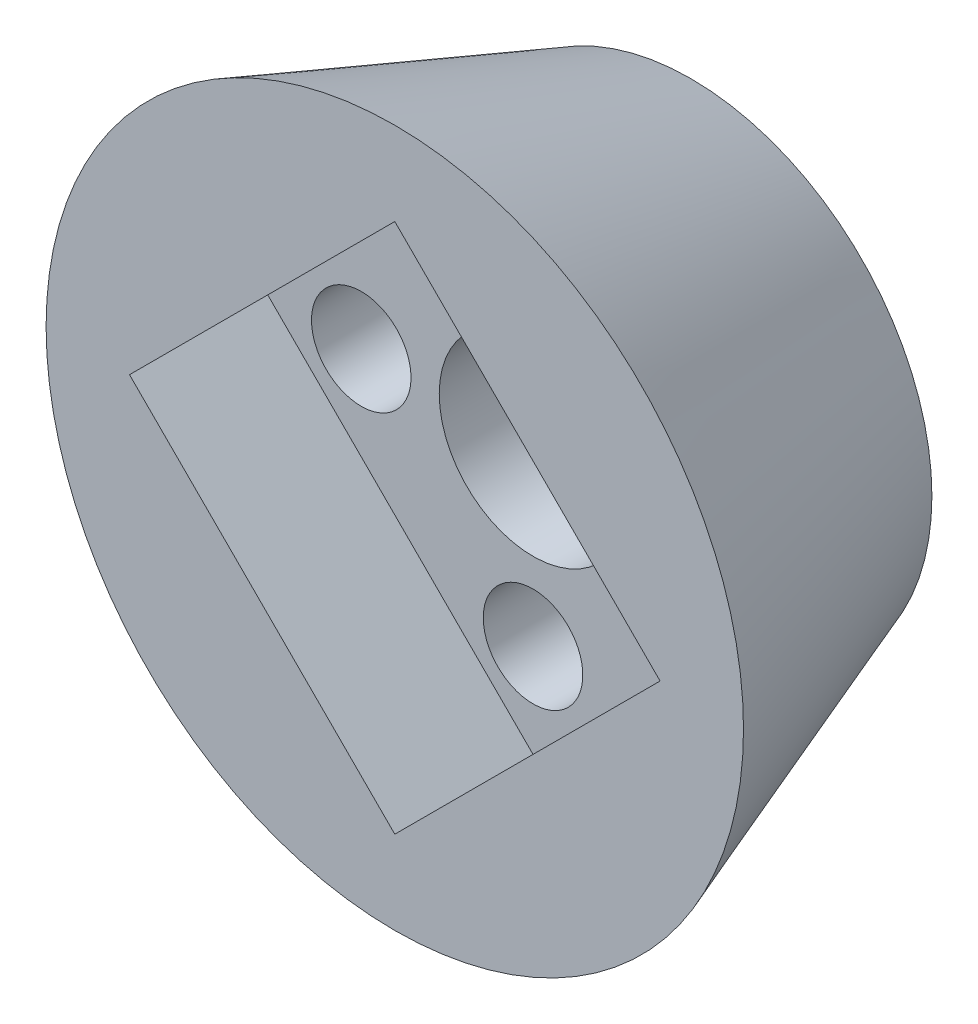
SolidWorks part; units mm, degrees
ref_plane "Front" through (0, 0, 0) normal (0, 0, 1) x (1, 0, 0)
ref_plane "Top" through (0, 0, 0) normal (0, 1, 0) x (1, 0, 0)
ref_plane "Right" through (0, 0, 0) normal (1, 0, 0) x (0, 0, -1)
sketch "GearFaceProfile" plane through (0, 0, 0) normal (0, 0, 1) x (1, 0, 0)
  circle A0 centre (0, 0) radius 12.2
  dimension "D1" = 24.4
extrude "GearFaceExtrude" add sketch "GearFaceProfile" along normal blind 15 draft 20 draft outward yes
sketch "CenterHoleProfile" plane through (0, 0, 0) normal (0, 0, -1) x (-1, 0, 0)
  circle A0 centre (0, 0) radius 4.75
  dimension "D1" = 9.5
extrude "CenterHoleCut" cut sketch "CenterHoleProfile" against normal through all
sketch "ScrewHoleProfile" plane through (0, 0, 0) normal (0, 0, -1) x (-1, 0, 0)
  line L0 (0, 0) -> (0, 8.7) construction
  line L1 (0, 0) -> (8.7, 0) construction
  line L2 (0, 0) -> (0, -8.7) construction
  line L3 (0, 0) -> (-8.7, 0) construction
  circle A2 centre (0, 8.7) radius 2.52
  circle A3 centre (8.7, 0) radius 2.52
  circle A4 centre (0, -8.7) radius 2.52
  circle A5 centre (-8.7, 0) radius 2.52
  dimension "D5" = 5.04
  dimension "D6" = 5.04
  dimension "D7" = 5.04
  dimension "D8" = 5.04
  dimension "D1" = 8.7
  dimension "D2" = 8.7
  dimension "D3" = 8.7
  dimension "D4" = 8.7
extrude "ScrewHoleCut" cut sketch "ScrewHoleProfile" against normal through all
sketch "ShaftCollarAttachmentProfile" plane through (0, 0, 15) normal (0, 0, 1) x (1, 0, 0)
  line L0 (0, 0) -> (0, 13.435) construction
  line L1 (0, 0) -> (13.435, 0) construction
  line L2 (0, 13.435) -> (13.435, 0)
  line L3 (13.435, 0) -> (0, -13.435)
  line L4 (0, -13.435) -> (-13.435, 0)
  line L5 (-13.435, 0) -> (0, 13.435)
  dimension "D1" = 19
  dimension "D2" = 19
extrude "ShaftCollarDockingCut" cut sketch "ShaftCollarAttachmentProfile" against normal blind 7
equation "\"TGMScrewHole-Center\"=8.70mm"
equation "\"TGMScrewHoleDiameter\"=5.04mm"
equation "\"TGMCenterHoleDiameter\"=9.50mm"
equation "\"TGMGearFaceDiameter\"=24.40mm"
equation "\"D1@GearFaceProfile\" = \"TGMGearFaceDiameter\""
equation "\"D1@CenterHoleProfile\" = \"TGMCenterHoleDiameter\""
equation "\"D4@ScrewHoleProfile\" = \"TGMScrewHole-Center\""
equation "\"D1@ScrewHoleProfile\" = \"TGMScrewHole-Center\""
equation "\"D2@ScrewHoleProfile\" = \"TGMScrewHole-Center\""
equation "\"D3@ScrewHoleProfile\" = \"TGMScrewHole-Center\""
equation "\"D5@ScrewHoleProfile\" = \"TGMScrewHoleDiameter\""
equation "\"D6@ScrewHoleProfile\" = \"TGMScrewHoleDiameter\""
equation "\"D8@ScrewHoleProfile\" = \"TGMScrewHoleDiameter\""
equation "\"D7@ScrewHoleProfile\" = \"TGMScrewHoleDiameter\""
equation "\"TGMCylinderLength\"=15.00mm"
equation "\"TGMShaftCollarSideLength\"=19.00mm"
equation "\"D1@ShaftCollarAttachmentProfile\" = \"TGMShaftCollarSideLength\""
equation "\"D2@ShaftCollarAttachmentProfile\" = \"TGMShaftCollarSideLength\""
equation "\"TGMShaftCollarDockingDepth\"=7.00mm"
equation "\"CageLeftBottomEdge\"=22.11mm"
equation "\"CageLeftTopEdge\"=22.11mm"
equation "\"CageRightBottomEdge\"=21.63mm"
equation "\"CageRightTopEdge\"=21.63mm"
equation "\"CageHeight\"=86.04mm"
equation "\"CageLength\"=73.76mm"
equation "\"CageTopScrewClearance\"=10mm"
equation "\"CageBottomScrewClearance\"=25mm"
equation "\"CageLeftTopDepth\"= 11.65mm"
equation "\"CageLeftBottomDepth\"=11.11mm"
equation "\"CageLeftTopHeight\"=8.56175mm"
equation "\"CageLeftBottomHeight\"=16mm"
equation "\"CageRightTopDepth\"= 11.05mm"
equation "\"CageRightBottomDepth\"=10.58mm"
equation "\"CageRightTopHeight\"=9.6mm"
equation "\"CageRightBottomHeight\"=15.49mm"
equation "\"CageLeftTopChannelDepth\"=2.41908mm"
equation "\"CageLeftBottomChannelDepth\"=2.588mm"
equation "\"CageLeftChannelHeight\"=11.7mm"
equation "\"CageRightTopChannelDepth\"=2.32mm"
equation "\"CageRightBottomChannelDepth\"=2.318mm"
equation "\"CageRightChannelHeight\"=10mm"
equation "\"CageChanRelHeight\"=23.99mm"
equation "\"CageChanRelDepth\"=5.492mm"
equation "\"CageChamberRadius\"=16.261mm"
equation "\"CageScrewDiameter\"=4.8mm"
equation "\"CageSetScrewDiameter\"=3.5mm"
equation "\"CageAxleRadius\"=6.639mm"
equation "\"CageAxleKeyHeight\"=1.619mm"
equation "\"CageAxleKeyWidth\"=2.662mm"
equation "\"CageHoseWindowWidth\"=16.29mm"
equation "\"CageHoseWindowHeight\"=26.5mm"
equation "\"CageHoseWindow-Edge\"=8.89mm"
equation "\"CageScrew-VerticalEdge\"=5.0mm"
equation "\"CageScrew-HorizontalEdge\"=7.5mm"
equation "\"CageScrew-HoseCornerScrewEdge\"=4.45mm"
equation "\"CageAxle-BottomEdge\"=56.05mm"
equation "\"CageAxle-FrontEdge\"=46.03mm"
equation "\"CageBackSetScrew-Axle\"=40mm"
equation "\"CageFrontSetScrew-Axle\"=22mm"
equation "\"CageVelocityWindow-BackEdge\"=34.8mm"
equation "\"CageVelocityWindow-BottomEdge\"=27.55mm"
equation "\"CageVelocityWindowHeight\"=22.29mm"
equation "\"CageVelocityWindowWidth\"=12.61mm"
equation "\"TriggerSlot-BottomEdge\"=6.35mm"
equation "\"TriggerSlot-FrontEdge\"=15mm"
equation "\"TriggerSlotSize\"=6.7mm"
equation "\"TriggerRackOffset\"=.236224in"
equation "\"TriggerSlotSizeInt\"=.25in"
equation "\"MotorMountLegLength\"=.25in"
equation "\"GearOffset\"=.264907in"
equation "\"TriggerSlotSpacing\"=.25in"
equation "\"TriggerMiniSlotWidth\"=3.5mm"
equation "\"TriggerRackWidth\"=6.5mm"
equation "\"whitemotordepth\"=11.27mm"
equation "\"whitemotorbackdepth\"=3.845mm"
equation "\"whitemotoraxledepth\" = 3.5mm"
equation "\"whitemotoraxleoffset\"=11.4mm"
equation "\"whitemotorwidth\"=12.07mm"
equation "\"whitemotorheight\"=16.68mm"
equation "\"whitemotorcylinderlength\" =13.04mm"
equation "\"whitemotorcylinderradius\"=3.845mm"
equation "\"whitemotorcylinderoffset\"=2.35mm"
equation "\"whitemotorcutoutlength\"=1.88mm"
equation "\"whitemotorouterrad\"=5mm"
equation "\"whitemotorinnerrad\"=2.95mm"
equation "\"elasticracklength\"=2in"
equation "\"elasticrackpegsize\"=.25in"
equation "\"elasticrackpegbuffer\"=.125in"
equation "\"elasticrackpegspacing\"=1.76476378in"
equation "\"elasticbaybuffer\"=.25in"
equation "\"elasticdepth\"=.125in"
equation "\"elasticbaydepth\"=.75in"
equation "\"motormountwidth\"=12mm"
equation "\"motormountcornerfillet\"=3mm"
